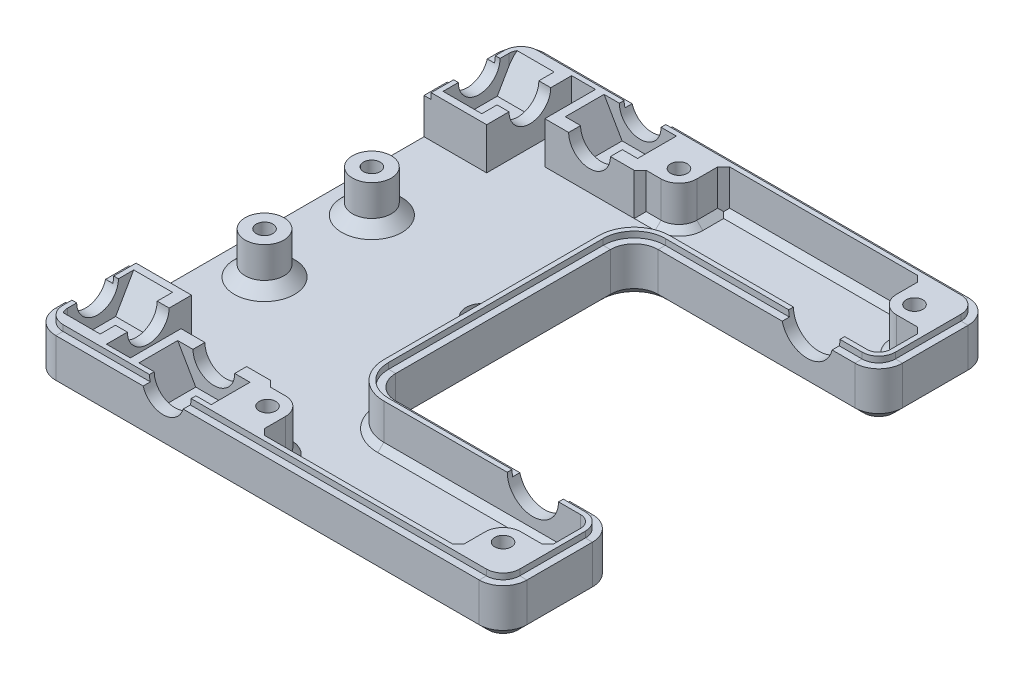
SolidWorks part; units mm, degrees
ref_plane "Front Plane" through (0, 0, 0) normal (0, 0, 1) x (1, 0, 0)
ref_plane "Top Plane" through (0, 0, 0) normal (0, 1, 0) x (1, 0, 0)
ref_plane "Right Plane" through (0, 0, 0) normal (1, 0, 0) x (0, 0, -1)
sketch "Sketch1" plane through (0, 0, 0) normal (0, 1, 0) x (1, 0, 0)
  line L1 (4, 22) -> (37, 22)
  line L2 (41, 26) -> (41, 37)
  line L3 (37, 41) -> (-34, 41)
  line L4 (-38, 37) -> (-38, -37)
  line L5 (-34, -41) -> (37, -41)
  line L6 (41, -37) -> (41, -26)
  line L7 (37, -22) -> (4, -22)
  line L9 (0, 18) -> (0, -18)
  arc A0 (41, 37) -> (37, 41) centre (37, 37) ccw
  arc A1 (37, 22) -> (41, 26) centre (37, 26) ccw
  arc A2 (37, -41) -> (41, -37) centre (37, -37) ccw
  arc A3 (41, -26) -> (37, -22) centre (37, -26) ccw
  arc A4 (4, -22) -> (0, -18) centre (4, -18) cw
  arc A5 (0, 18) -> (4, 22) centre (4, 18) cw
  arc A6 (-34, 41) -> (-38, 37) centre (-34, 37) ccw
  arc A7 (-38, -37) -> (-34, -41) centre (-34, -37) ccw
  point P0 (0, 0)
  point P13 (41, 41)
  point P16 (41, 22)
  point P23 (0, -22)
  point P26 (0, 22)
  dimension "D5" = 4
  dimension "D1" = 44
  dimension "D2" = 41
  dimension "D3" = 19
  dimension "D4" = 38
extrude "Boss-Extrude1" add sketch "Sketch1" along normal blind 9
shell "Shell1" thickness 2 removed face at (11, 9, 0)
sketch "Esboço5" plane through (0, 0, 0) normal (0, 0, 1) x (1, 0, 0)
  line L0 (-38, 9) -> (-36.8, 9)
  line L1 (-36.8, 9) -> (-36.8, 8)
  line L2 (-36.8, 8) -> (-38, 8)
  line L3 (-38, 8) -> (-38, 9)
  dimension "D1" = 1
  dimension "D2" = 1.2
sketch "Esboço6" plane through (0, 9, 0) normal (0, 1, 0) x (1, 0, 0)
  line L8 (37, 41) -> (-34, 41)
  line L9 (-38, 37) -> (-38, -37)
  line L10 (-34, -41) -> (37, -41)
  line L11 (41, -37) -> (41, -26)
  line L12 (37, -22) -> (4, -22)
  line L13 (0, -18) -> (0, 18)
  line L14 (4, 22) -> (37, 22)
  line L15 (41, 26) -> (41, 37)
  line L16 (37, 41) -> (-34, 41)
  line L17 (-38, 37) -> (-38, -37)
  line L18 (-34, -41) -> (37, -41)
  line L19 (41, -37) -> (41, -26)
  line L20 (37, -22) -> (4, -22)
  line L21 (0, -18) -> (0, 18)
  line L22 (4, 22) -> (37, 22)
  line L23 (41, 26) -> (41, 37)
  arc A8 (41, 37) -> (37, 41) centre (37, 37) ccw
  arc A9 (-34, 41) -> (-38, 37) centre (-34, 37) ccw
  arc A10 (-38, -37) -> (-34, -41) centre (-34, -37) ccw
  arc A11 (37, -41) -> (41, -37) centre (37, -37) ccw
  arc A12 (41, -26) -> (37, -22) centre (37, -26) ccw
  arc A13 (0, -18) -> (4, -22) centre (4, -18) ccw
  arc A14 (4, 22) -> (0, 18) centre (4, 18) ccw
  arc A15 (37, 22) -> (41, 26) centre (37, 26) ccw
  arc A16 (41, 37) -> (37, 41) centre (37, 37) ccw
  arc A17 (-34, 41) -> (-38, 37) centre (-34, 37) ccw
  arc A18 (-38, -37) -> (-34, -41) centre (-34, -37) ccw
  arc A19 (37, -41) -> (41, -37) centre (37, -37) ccw
  arc A20 (41, -26) -> (37, -22) centre (37, -26) ccw
  arc A21 (0, -18) -> (4, -22) centre (4, -18) ccw
  arc A22 (4, 22) -> (0, 18) centre (4, 18) ccw
  arc A23 (37, 22) -> (41, 26) centre (37, 26) ccw
  dimension "D1" = 0
chamfer "Chamfer1" distance 1 angle 45 16 edges at (-35.4142, 2, 38.4142) (-36, 2, 0) (-35.4142, 2, -38.4142) (1.5, 2, -39) (38.4142, 2, -38.4142) (39, 2, -31.5) (38.4142, 2, -24.5858) (20.5, 2, -24) (-0.2426, 2, -22.2426) (-2, 2, 0) (-0.2426, 2, 22.2426) (20.5, 2, 24) (38.4142, 2, 24.5858) (39, 2, 31.5) (38.4142, 2, 38.4142) (1.5, 2, 39)
sketch "Sketch6" plane through (0, 0, 0) normal (0, 0, 1) x (1, 0, 0)
  line L0 (41, 9) -> (41, 0) construction
  line L1 (-34, 9) -> (37, 9) construction
  circle A0 centre (29, 9) radius 4.3
  dimension "D2" = 8.6
  dimension "D1" = 12
sketch "Esboço3" plane through (-38, 0, 0) normal (-1, 0, 0) x (0, 0, 1)
  line L1 (-24.75, 2) -> (24.75, 2)
  line L2 (-24.75, 2) -> (-24.75, 16)
  line L3 (-24.75, 16) -> (24.75, 16)
  line L4 (24.75, 2) -> (24.75, 16)
  line L5 (-37, 9) -> (37, 9) construction
  point P6 (0, 16)
  point P9 (24.75, 9)
  dimension "D1" = 49.5
  dimension "D2" = 14
sweep "Varredura de corte2" cut profiles "Esboço5" path "Esboço6"
extrude "Cut-Extrude1" cut sketch "Sketch6" along normal blind 27 and the other way blind 27 contours A0 region at (29, 9, 0)
sketch "Sketch9" plane through (0, 0, 41) normal (0, 0, 1) x (1, 0, 0)
  line L0 (-34, 9) -> (37, 9) construction
  line L1 (-12.9689, 3.75) -> (-9.9378, 9)
  line L2 (-9.9378, 9) -> (-12.9689, 14.25)
  line L3 (-12.9689, 14.25) -> (-19.0311, 14.25)
  line L4 (-19.0311, 14.25) -> (-22.0622, 9)
  line L5 (-22.0622, 9) -> (-19.0311, 3.75)
  line L6 (-19.0311, 3.75) -> (-12.9689, 3.75)
  line L7 (-23.5, 9) -> (-8.5, 9)
  line L8 (-38, 8) -> (-38, 0) construction
  line L10 (-23.5, 16) -> (-8.5, 16)
  line L11 (-23.5, 16) -> (-23.5, 2)
  line L12 (-23.5, 2) -> (-8.5, 2)
  line L13 (-8.5, 16) -> (-8.5, 2)
  line L14 (-23.5, 16) -> (-8.5, 2) construction
  line L15 (-23.5, 2) -> (-8.5, 16) construction
  line L16 (38, 2) -> (37, 2) construction
  circle A0 centre (-16, 9) radius 5.25 construction
  circle A2 centre (-16, 9) radius 3.5
  line M26 (37, 8) -> (-34, 8)
  dimension "D2" = 15
  dimension "D4" = 7
  dimension "D1" = 10.5
  dimension "D3" = 22
extrude "Boss-Extrude6" add sketch "Sketch9" against normal blind 6.5 from offset 2 contours L13 L1 L6 L5 L11 | L7 L11 L5 M26 | L13 L7 L1 M26 region at (-11.6021, 5.7942, 41) region at (-9.3713, 8.4721, 41) region at (-22.6287, 8.4721, 41) offset against normal yes
extrude "Boss-Extrude7" add sketch "Sketch9<4>" against normal blind 2 from surface contours L13 L1 L6 L5 L11 | A2 L5 L6 L1 | L7 L11 L5 M26 | A2 L7 L5 M26 | L13 L7 L1 M26 | A2 L1 L7 M26 region at (-16, 3.8676, 41) region at (-11.6021, 5.7942, 41) region at (-11.3818, 8.5155, 41) region at (-9.3713, 8.4721, 41) region at (-22.6287, 8.4721, 41) region at (-20.6182, 8.5155, 41) starting at face at (-16, 5.9375, 32.5)
sketch "Sketch9<4>" plane through (0, 0, 41) normal (0, 0, 1) x (1, 0, 0) same geometry as "Sketch9"
mirror "Mirror5" about plane through (0, 0, 0) normal (0, 0, 1) of "Boss-Extrude6"
extrude "Boss-Extrude8" add sketch "Sketch9<5>" along normal blind 2 from surface contours L13 L1 L6 L5 L11 | A2 L5 L6 L1 | L13 L7 L1 M26 | A2 L1 L7 M26 | A2 L7 L5 M26 | L7 L11 L5 M26 region at (-16, 3.8676, 41) region at (-11.6021, 5.7942, 41) region at (-11.3818, 8.5155, 41) region at (-9.3713, 8.4721, 41) region at (-22.6287, 8.4721, 41) region at (-20.6182, 8.5155, 41) starting at face at (-16, 5.9375, -32.5)
sketch "Sketch9<5>" plane through (0, 0, 41) normal (0, 0, 1) x (1, 0, 0) same geometry as "Sketch9"
extrude "Cut-Extrude3" cut sketch "Sketch9<3>" against normal through all contours L7 A2 | A2 M26 region at (-16, 8.5035, 41) region at (-16, 6.9612, 41)
sketch "Sketch9<3>" plane through (0, 0, 41) normal (0, 0, 1) x (1, 0, 0) same geometry as "Sketch9"
sketch "Sketch10" plane through (-38, 0, 0) normal (-1, 0, 0) x (0, 0, 1)
  line L6 (24.5, 9) -> (39.5, 9)
  line L7 (24.5, 16) -> (39.5, 16)
  line L8 (24.5, 16) -> (24.5, 2)
  line L9 (24.5, 2) -> (39.5, 2)
  line L10 (39.5, 16) -> (39.5, 2)
  line L11 (24.5, 16) -> (39.5, 2) construction
  line L12 (24.5, 2) -> (39.5, 16) construction
  line L13 (41, 8) -> (41, 0) construction
  line L14 (35.0311, 14.25) -> (28.9689, 14.25)
  line L15 (28.9689, 14.25) -> (25.9378, 9)
  line L16 (25.9378, 9) -> (28.9689, 3.75)
  line L17 (28.9689, 3.75) -> (35.0311, 3.75)
  line L18 (35.0311, 3.75) -> (38.0622, 9)
  line L19 (38.0622, 9) -> (35.0311, 14.25)
  line L20 (-30.5, 2) -> (-38, 2) construction
  line L23 (37, 9) -> (0, 9) construction
  circle A1 centre (32, 9) radius 3.5
  circle A2 centre (32, 9) radius 5.25 construction
  line M20 (37, 0) -> (37, 8)
  line M43 (37, 8) -> (0, 8)
  dimension "D3" = 7
  dimension "D1" = 10.5
  dimension "D2" = 15
  dimension "D4" = 9
extrude "Boss-Extrude9" add sketch "Sketch10" along normal up to body from offset 10.5 contours L18 L17 L16 L6 L8 L10 | L18 L9 L10 L6 M20 | L16 L6 L8 M43 region at (-38, 8.4721, 25.3713) region at (-38, 7.8613, 25.5076) region at (-38, 5.3293, 38.303) offset against normal yes
extrude "Boss-Extrude10" add sketch "Sketch10<3>" along normal blind 2 from surface contours L18 L17 L16 L6 L8 L10 | L18 L9 L10 L6 M20 | A1 L16 L17 L18 M20 | L18 L6 M20 | A1 L6 L16 M43 | L16 L6 L8 M43 region at (-38, 8.4721, 25.3713) region at (-38, 8.5155, 27.3818) region at (-38, 7.8613, 25.5076) region at (-38, 7.8869, 27.5805) region at (-38, 8.4514, 36.662) region at (-38, 5.3293, 38.303) starting at face at (-27.5, 5.6111, 32.5556)
sketch "Sketch10<3>" plane through (-38, 0, 0) normal (-1, 0, 0) x (0, 0, 1) same geometry as "Sketch10"
extrude "Cut-Extrude4" cut sketch "Sketch10<4>" against normal blind 11 contours A1
sketch "Sketch10<4>" plane through (-38, 0, 0) normal (-1, 0, 0) x (0, 0, 1) same geometry as "Sketch10"
mirror "Mirror6" about plane through (0, 0, 0) normal (0, 0, 1) of "Cut-Extrude4", "Boss-Extrude10", "Boss-Extrude9"
sketch "Esboço1" plane through (0, 0, 0) normal (0, -1, 0) x (1, 0, 0)
  line L0 (-23, -25.9392) -> (-23, 25.9392) construction
  line L1 (-12, -30.0516) -> (-12, 30.0516) construction
  line L2 (-18.6273, 4.1566) -> (-18.6273, 4.9624)
  line L3 (-18.6273, 4.9624) -> (-20.109, 5.9391)
  line L4 (-20.109, 5.9391) -> (-20.109, 5.1333)
  line L5 (-20.109, 5.1333) -> (-18.6273, 4.1566)
  text T0 "<i>DFTE</i>" font "@Adobe Gothic Std B" height 9
  text T1 "<b>SENSOR OPTICO</b>" font "@Adobe Gothic Std B" height 6
  point P5 (-23, 0)
  point P6 (-12, 0)
  point P23 (-20.109, 5.5362)
  dimension "D1" = 23
  dimension "D2" = 12
extrude "Corte-extrusão1" cut sketch "Esboço1" against normal blind 0.7
sketch "Esboço2" plane through (0, 2, 0) normal (0, 1, 0) x (1, 0, 0)
  line L1 (0, -18) -> (0, 18) construction
  line L2 (37, 41) -> (-19.5, 41) construction
  circle A0 centre (-7, 3.5) radius 2.7
  dimension "D3" = 5.4
  dimension "D1" = 37.5
  dimension "D2" = 7
extrude "Corte-extrusão2" cut sketch "Esboço2" against normal blind 10 contours A0
extrude "Corte-extrusão3" cut sketch "Esboço3" against normal blind 12
sketch "Esboço4" plane through (0, 2, 0) normal (0, 1, 0) x (1, 0, 0)
  line L0 (-2, 34.5) -> (-2, 39)
  line L1 (37, 39) -> (-8.5, 39) construction
  line L2 (-2, 39) -> (-8.5, 39)
  line L3 (0, 0) -> (-38, 0) construction
  line L4 (31.5, 34.5) -> (31.5, 39)
  line L5 (34.5, 31.5) -> (39, 31.5)
  line L6 (39, 26) -> (39, 37) construction
  line L7 (39, 31.5) -> (39, 37)
  line L8 (37, 39) -> (31.5, 39)
  line L9 (37, -39) -> (31.5, -39)
  line L10 (39, -31.5) -> (39, -37)
  line L11 (34.5, -31.5) -> (39, -31.5)
  line L12 (31.5, -34.5) -> (31.5, -39)
  line L13 (-5, 31.5) -> (-8.5, 31.5)
  line L14 (-2, -39) -> (-8.5, -39)
  line L15 (-2, -34.5) -> (-2, -39)
  line L16 (-5, -31.5) -> (-8.5, -31.5)
  line L18 (-8.5, -31.5) -> (-8.5, -39)
  line L19 (-8.5, 30.5) -> (-8.5, 38) construction
  line L20 (-8.5, 31.5) -> (-8.5, 39)
  line L21 (41, 26) -> (41, 37) construction
  line L22 (37, 41) -> (-19.5, 41) construction
  line L23 (-38, 24.75) -> (-38, -24.75) construction
  line L24 (37, -39) -> (-8.5, -39) construction
  line L25 (39, -26) -> (39, -37) construction
  arc A17 (39, 37) -> (37, 39) centre (37, 37) ccw construction
  arc A18 (39, 37) -> (37, 39) centre (37, 37) ccw
  arc A19 (37, -39) -> (39, -37) centre (37, -37) ccw construction
  circle A20 centre (-31, 34.5) radius 3 construction
  circle A21 centre (34.5, 34.5) radius 3
  circle A22 centre (-31, -34.5) radius 3 construction
  circle A23 centre (34.5, -34.5) radius 3
  circle A24 centre (-31, 34.5) radius 1.4 construction
  circle A25 centre (34.5, 34.5) radius 1.4
  circle A26 centre (-31, -34.5) radius 1.4 construction
  circle A27 centre (34.5, -34.5) radius 1.4
  circle A28 centre (-31, 9) radius 3.25
  circle A29 centre (-31, 9) radius 1.4
  circle A30 centre (-31, -9) radius 1.4
  circle A31 centre (-31, -9) radius 3.25
  circle A32 centre (-5, 34.5) radius 1.4
  circle A33 centre (-5, -34.5) radius 3
  circle A34 centre (-5, -34.5) radius 1.4
  circle A35 centre (-5, 34.5) radius 3
  arc A36 (37, -39) -> (39, -37) centre (37, -37) ccw
  point P15 (-31, -5.75)
  point P49 (-31, 5.75)
  point P53 (-31, -12.25)
  point P71 (0, 0)
  point P74 (-27.75, 9)
  point P89 (-34, 9)
  line M27 (-8.5, -38) -> (37, -38)
  arc M28 (37, -38) -> (38, -37) centre (37, -37) ccw
  line M29 (38, -37) -> (38, -26)
  line M37 (38, 26) -> (38, 37)
  arc M38 (38, 37) -> (37, 38) centre (37, 37) ccw
  line M39 (37, 38) -> (-8.5, 38)
  dimension "D1" = 6.5
  dimension "D5" = 2.8
  dimension "D6" = 6
  dimension "D2" = 3.5
  dimension "D3" = 6.5
  dimension "D4" = 6.5
  dimension "D7" = 18
  dimension "D8" = 7
extrude "Ressalto-extrusão1" add sketch "Esboço4" along normal blind 7 contours A35 A32 | A21 A25 | A33 A34 | A23 A27 | A31 A30 | A28 A29 region at (-2.9387, 2, -32.4387) region at (34.5, 2, -37.4151) region at (32.4387, 2, 32.4387) region at (-7.0613, 2, 36.5613) region at (-34.1581, 2, -9) region at (-34.1581, 2, 9)
chamfer "Chanfro1" distance 1.8 angle 45 2 edges at (-31, 2, -5.75) (-31, 2, 12.25)
extrude "Ressalto-extrusão2" add sketch "Esboço4<2>" along normal up to surface (7 mm away) contours A35 L0 M39 | A21 L5 L4 M37 M38 M39 | L10 L11 L12 L9 M29 M28 M27 | A33 L15 M27 | A23 L12 L11 M27 M28 M29 | L15 L14 M27 | L2 L0 M39 | L7 A18 L8 L4 L5 M39 M38 M37 region at (-7.1863, 2, -36.6863) region at (31.6061, 2, -38.5) region at (34.25, 2, -37.9081) region at (-5.25, 2, -38.5) region at (-5.25, 2, 38.5) region at (-5.25, 2, 37.9081) region at (34.25, 2, 38.8939) region at (31.5919, 2, 36.25) up to face at (15.9618, 9, 32.3333)
sketch "Esboço4<2>" plane through (0, 2, 0) normal (0, 1, 0) x (1, 0, 0) same geometry as "Esboço4"
chamfer "Chanfro2" distance 1 angle 45 20 edges at (39, 6, -31.5) (31.5, 6, -39) (36.25, 2, -31.5) (32.3787, 2, -32.3787) (31.5, 2, -36.25) (-2, 6, -39) (-2, 2, -36.25) (-2.8787, 2, -32.3787) (39, 6, 31.5) (31.5, 6, 39) (31.5, 2, 36.25) (32.3787, 2, 32.3787) (36.25, 2, 31.5) (-2.8787, 2, 32.3787) (-2, 2, 36.25) (-2, 6, 39) (-6.75, 2, -31.5) (-6.75, 2, 31.5) (-8.5, 5.5, 31.5) (-8.5, 5.5, -31.5)
chamfer "Chanfro3" distance 1.5 angle 45 16 edges at (20.5, 0, 22) (1.1716, 0, 20.8284) (39.8284, 0, 23.1716) (0, 0, 0) (41, 0, 31.5) (1.1716, 0, -20.8284) (39.8284, 0, 39.8284) (20.5, 0, -22) (1.5, 0, 41) (39.8284, 0, -23.1716) (-36.8284, 0, 39.8284) (41, 0, -31.5) (-38, 0, 0) (39.8284, 0, -39.8284) (-36.8284, 0, -39.8284) (1.5, 0, -41)
